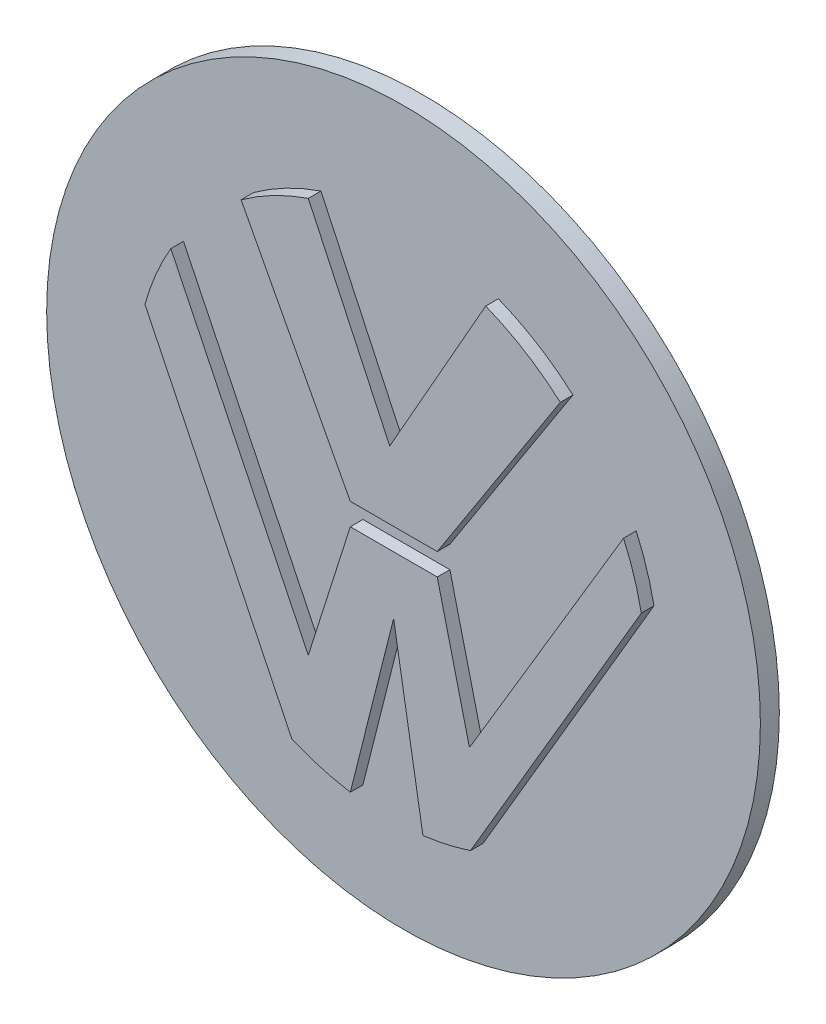
SolidWorks part; units mm, degrees
ref_plane "Front Plane" through (0, 0, 0) normal (0, 0, 1) x (1, 0, 0)
ref_plane "Top Plane" through (0, 0, 0) normal (0, 1, 0) x (1, 0, 0)
ref_plane "Right Plane" through (0, 0, 0) normal (1, 0, 0) x (0, 0, -1)
sketch "Sketch1" plane through (0, 0, 0) normal (0, 0, 1) x (1, 0, 0)
  line L0 (-30.0911, 41.4905) -> (-8.1511, 0)
  line L1 (-8.1511, 0) -> (9.3156, 0)
  line L2 (9.3156, 0) -> (34.0363, 38.3206)
  line L3 (0.5545, -16.0203) -> (6.44, -50.8475)
  line L4 (-0.2263, 13.5883) -> (19.0523, 47.5809)
  line L5 (50.3117, 9.7814) -> (15.9928, -48.6946)
  line L6 (-8.1511, -50.6014) -> (0.5545, -16.0203)
  line L7 (-0.2263, 13.5883) -> (-16.5903, 48.4943)
  line L10 (-19.8789, -47.2416) -> (-49.404, 13.6449)
  line L12 (-44.2033, 25.9424) -> (-16.5903, -31.001)
  line L13 (-8.1511, -4.4249) -> (9.3156, -4.4249)
  line L14 (46.7393, 21.0327) -> (15.7847, -30.8775)
  line L15 (15.7847, -30.8775) -> (9.3156, -4.4249)
  line L16 (-16.5903, -31.001) -> (-8.1511, -4.4249)
  circle A0 centre (0, 0) radius 58.9905
  circle A1 centre (0, 0) radius 51.2537
  circle A2 centre (0, 0) radius 71.6905
  dimension "D9" = 12.7
  dimension "D1" = 10.0452
  dimension "D2" = 40
  dimension "D3" = 40
  dimension "D4" = 0.4
  dimension "D5" = 2.018
  dimension "D6" = 2
extrude "Boss-Extrude4" add sketch "Sketch1" along normal blind 3.81 contours A0 A1 region at (-57.322, 0, 0)
extrude "Boss-Extrude8" add sketch "Sketch1<5>" along normal blind 6.35 contours L2 A1 L0 L1 region at (-23.2317, 44.7823, 0)
sketch "Sketch1<5>" plane through (0, 0, 0) normal (0, 0, 1) x (1, 0, 0) same geometry as "Sketch1"
extrude "Boss-Extrude11" add sketch "Sketch1<7>" along normal blind 6.35 contours L5 A1 L14 L15 L13 L16 L12 L10 L6 L3 region at (-1.5019, -18.5793, 0)
sketch "Sketch1<7>" plane through (0, 0, 0) normal (0, 0, 1) x (1, 0, 0) same geometry as "Sketch1"
extrude "Boss-Extrude12" add sketch "Sketch1<8>" along normal blind 1.27 contours L2 A1 L0 L1 region at (-23.2317, 44.7823, 0)
sketch "Sketch1<8>" plane through (0, 0, 0) normal (0, 0, 1) x (1, 0, 0) same geometry as "Sketch1"
sketch "Sketch2" plane through (0, 0, 6.35) normal (0, 0, 1) x (1, 0, 0)
extrude "Boss-Extrude13" add sketch "Sketch1<9>" along normal blind 3.81 contours L5 A1 L14 L15 L13 L16 L12 L10 L6 L3 | L2 A1 L0 L1 region at (-23.2317, 44.7823, 0) region at (-1.5019, -18.5793, 0)
sketch "Sketch1<9>" plane through (0, 0, 0) normal (0, 0, 1) x (1, 0, 0) same geometry as "Sketch1"
extrude "Boss-Extrude14" add sketch "Sketch1<10>" along normal blind 3.81 contours A2
sketch "Sketch1<10>" plane through (0, 0, 0) normal (0, 0, 1) x (1, 0, 0) same geometry as "Sketch1"
sketch "Sketch3" plane through (0, 0, 3.81) normal (0, 0, 1) x (1, 0, 0)
